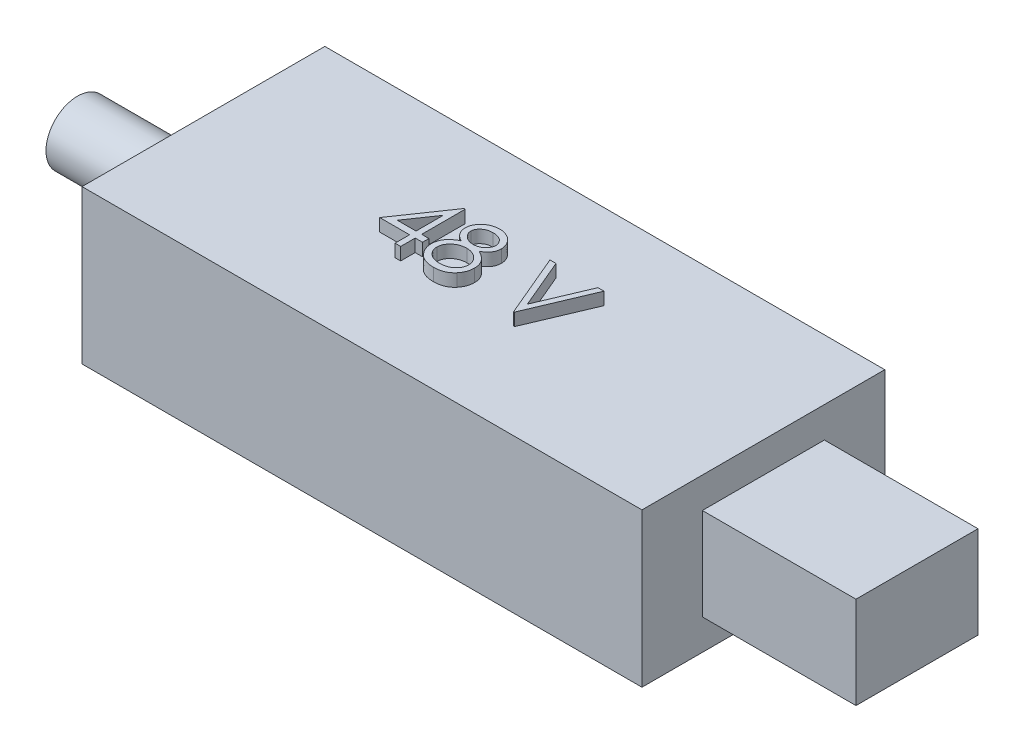
SolidWorks part; units mm, degrees
ref_plane "Front Plane" through (0, 0, 0) normal (0, 0, 1) x (1, 0, 0)
ref_plane "Top Plane" through (0, 0, 0) normal (0, 1, 0) x (1, 0, 0)
ref_plane "Right Plane" through (0, 0, 0) normal (1, 0, 0) x (0, 0, -1)
sketch "Sketch1" plane through (0, 0, 0) normal (0, 1, 0) x (1, 0, 0)
  line L1 (-56.5, 24.5) -> (56.5, 24.5)
  line L2 (-56.5, 24.5) -> (-56.5, -24.5)
  line L3 (-56.5, -24.5) -> (56.5, -24.5)
  line L4 (56.5, 24.5) -> (56.5, -24.5)
  line L5 (-56.5, 24.5) -> (56.5, -24.5) construction
  line L6 (-56.5, -24.5) -> (56.5, 24.5) construction
  point P0 (0, 0)
  dimension "D1" = 113
  dimension "D2" = 49
extrude "Boss-Extrude1" add sketch "Sketch1" along normal blind 31
sketch "Sketch2" plane through (56.5, 0, 0) normal (1, 0, 0) x (0, 0, -1)
  line L0 (-24.5, 15.5) -> (24.5, 15.5) construction
  line L1 (-24.5, 31) -> (-24.5, 0) construction
  line L2 (24.5, 31) -> (24.5, 0) construction
  line L4 (-12.3134, 24.7992) -> (12.3134, 24.7992)
  line L5 (-12.3134, 24.7992) -> (-12.3134, 6.2008)
  line L6 (-12.3134, 6.2008) -> (12.3134, 6.2008)
  line L7 (12.3134, 24.7992) -> (12.3134, 6.2008)
  line L8 (-12.3134, 24.7992) -> (12.3134, 6.2008) construction
  line L9 (-12.3134, 6.2008) -> (12.3134, 24.7992) construction
  point P6 (0, 15.5)
extrude "Boss-Extrude2" add sketch "Sketch2" along normal blind 31
sketch "Sketch3" plane through (-56.5, 0, 0) normal (-1, 0, 0) x (0, 0, 1)
  line L0 (-24.5, 15.5) -> (24.5, 15.5) construction
  line L1 (-24.5, 31) -> (-24.5, 0) construction
  line L2 (24.5, 31) -> (24.5, 0) construction
  circle A0 centre (0, 15.5) radius 6.3685
extrude "Boss-Extrude3" add sketch "Sketch3" along normal blind 25.4
sketch "Sketch5" plane through (0, 31, 0) normal (0, 1, 0) x (1, 0, 0)
  text T0 "48 V" font "Century Gothic" height 12.7
extrude "Boss-Extrude4" add sketch "Sketch5" along normal blind 2.54
